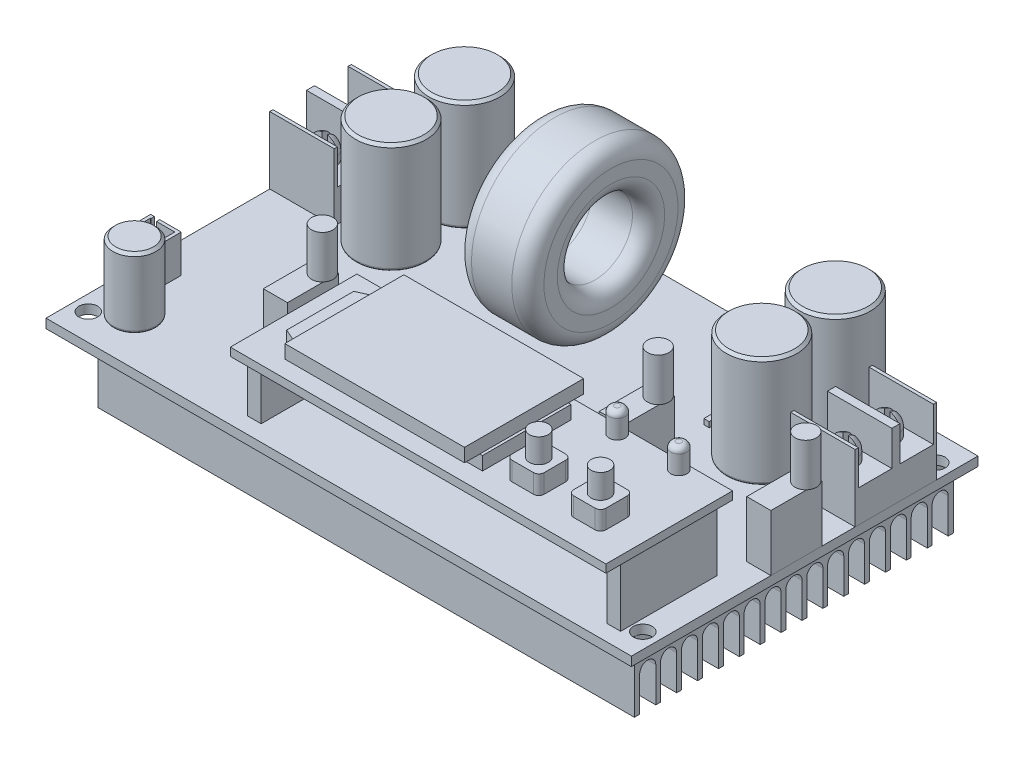
SolidWorks part; units mm, degrees
ref_plane "Alzado" through (0, 0, 0) normal (0, 0, 1) x (1, 0, 0)
ref_plane "Planta" through (0, 0, 0) normal (0, 1, 0) x (1, 0, 0)
ref_plane "Vista lateral" through (0, 0, 0) normal (1, 0, 0) x (0, 0, -1)
sketch "Croquis1" plane through (0, 0, 0) normal (0, 1, 0) x (1, 0, 0)
  line L0 (0, -32.3) -> (0, 32.3) construction
  line L1 (-54.55, 32.3) -> (54.55, 32.3)
  line L2 (-54.55, 32.3) -> (-54.55, -32.3)
  line L3 (-54.55, -32.3) -> (54.55, -32.3)
  line L4 (54.55, 32.3) -> (54.55, -32.3)
  line L5 (-54.55, 32.3) -> (54.55, -32.3) construction
  line L6 (-54.55, -32.3) -> (54.55, 32.3) construction
  line L7 (-54.55, 0) -> (54.55, 0) construction
  circle A0 centre (51.675, 27.3) radius 1.75
  circle A1 centre (51.675, -27.3) radius 1.75
  circle A2 centre (-51.675, -27.3) radius 1.75
  circle A3 centre (-51.675, 27.3) radius 1.75
  point P0 (0, 0)
  point P9 (0, 0)
  point P12 (0, 0)
  dimension "D3" = 3.5
  dimension "D1" = 109.1
  dimension "D2" = 64.6
  dimension "D4" = 5
  dimension "D5" = 103.35
extrude "Saliente-Extruir1" add sketch "Croquis1" along normal blind 1.7
sketch "Croquis2" plane through (0, 1.7, 0) normal (0, 1, 0) x (1, 0, 0)
  line L0 (54.55, 32.3) -> (-54.55, 32.3) construction
  line L2 (-54.55, 32.3) -> (-54.55, -32.3) construction
  circle A0 centre (-34.55, 25.7) radius 6.6
  circle A1 centre (-34.55, 12) radius 6.6
  point P8 (-34.55, 32.3)
  point P10 (-34.55, 19.1)
  point P18 (-34.55, 19.1)
  point P25 (-34.55, 18.6)
  dimension "D1" = 13.2
  dimension "D3" = 20
  dimension "D4" = 0.5
extrude "Saliente-Extruir4" add sketch "Croquis2" along normal blind 20.5 separate body
sketch "Croquis3" plane through (0, 1.7, 0) normal (0, 1, 0) x (1, 0, 0)
  line L0 (-54.55, 32.3) -> (-54.55, -32.3) construction
  line L1 (-54.55, 24.6) -> (-42.55, 24.6)
  line L2 (-54.55, 24.6) -> (-54.55, 9.4)
  line L3 (-54.55, 9.4) -> (-42.55, 9.4)
  line L4 (-42.55, 24.6) -> (-42.55, 9.4)
  line L5 (54.55, 32.3) -> (-54.55, 32.3) construction
  dimension "D1" = 15.2
  dimension "D2" = 12
  dimension "D3" = 7.7
extrude "Saliente-Extruir5" add sketch "Croquis3" along normal blind 6 separate body
sketch "Croquis4" plane through (0, 7.7, 0) normal (0, 1, 0) x (1, 0, 0)
  line L1 (-54.55, 24.6) -> (-42.55, 24.6)
  line L2 (-54.55, 24.6) -> (-54.55, 24)
  line L3 (-54.55, 24) -> (-42.55, 24)
  line L4 (-42.55, 24.6) -> (-42.55, 24)
  line L5 (-54.55, 24.6) -> (-54.55, 9.4) construction
  line L10 (-54.55, 17.75) -> (-42.55, 17.75)
  line L11 (-54.55, 17.75) -> (-54.55, 16.25)
  line L12 (-54.55, 16.25) -> (-42.55, 16.25)
  line L13 (-42.55, 17.75) -> (-42.55, 16.25)
  line L14 (-54.55, 17) -> (-42.55, 17) construction
  line L15 (-54.55, 10) -> (-42.55, 10)
  line L16 (-42.55, 9.4) -> (-42.55, 10)
  line L17 (-54.55, 9.4) -> (-42.55, 9.4)
  line L18 (-54.55, 9.4) -> (-54.55, 10)
  line L19 (-42.55, 9.4) -> (-42.55, 24.6) construction
  point P20 (-54.55, 17)
  point P22 (-54.55, 17)
  dimension "D1" = 1.5
  dimension "D2" = 0.6
extrude "Saliente-Extruir6" add sketch "Croquis4" along normal blind 6.5 separate body
combine bodies "Combinar1" operation type add bodies to combine 103 105 106 104
sketch "Croquis5" plane through (0, 7.7, 0) normal (0, 1, 0) x (1, 0, 0)
  line L0 (-42.55, 17.75) -> (-42.55, 24) construction
  line L1 (-42.55, 24.6) -> (-54.55, 24.6) construction
  line L2 (-54.55, 17) -> (-42.55, 17) construction
  line L3 (-54.55, 17.75) -> (-54.55, 16.25) construction
  line L4 (-42.55, 16.25) -> (-42.55, 17.75) construction
  circle A0 centre (-48.55, 20.875) radius 2.5
  circle A1 centre (-48.55, 13.125) radius 2.5
  point P2 (-48.55, 24.6)
  point P3 (-42.55, 20.875)
  dimension "D1" = 5
extrude "Saliente-Extruir7" add sketch "Croquis5" along normal blind 4
fillet "Redondeo1" radius 2.5 2 edges at (-48.55, 11.7, -15.625) (-48.55, 11.7, -18.375)
ref_plane "Plano1" through (0, 12.2, 0) normal (0, 1, 0) x (1, 0, 0)
sketch "Croquis6" plane through (0, 12.2, 0) normal (0, 1, 0) x (1, 0, 0)
  line L0 (-48.05, 21.375) -> (-46.1005, 21.375)
  line L1 (-49.05, 23.3245) -> (-48.05, 23.3245)
  line L2 (-49.05, 23.3245) -> (-49.05, 21.375)
  line L3 (-49.05, 18.4255) -> (-48.05, 18.4255)
  line L4 (-48.05, 23.3245) -> (-48.05, 21.375)
  line L5 (-50.9995, 21.375) -> (-49.05, 21.375)
  line L6 (-50.9995, 21.375) -> (-50.9995, 20.375)
  line L7 (-50.9995, 20.375) -> (-49.05, 20.375)
  line L8 (-46.1005, 21.375) -> (-46.1005, 20.375)
  line L9 (-49.05, 20.375) -> (-49.05, 18.4255)
  line L10 (-48.05, 20.375) -> (-46.1005, 20.375)
  line L11 (-48.05, 20.375) -> (-48.05, 18.4255)
  line L12 (-54.55, 17) -> (-42.55, 17) construction
  line L13 (-54.55, 17.75) -> (-54.55, 16.25) construction
  line L15 (-48.05, 13.625) -> (-48.05, 15.5745)
  line L16 (-48.05, 13.625) -> (-46.1005, 13.625)
  line L17 (-49.05, 13.625) -> (-49.05, 15.5745)
  line L18 (-46.1005, 12.625) -> (-46.1005, 13.625)
  line L19 (-50.9995, 13.625) -> (-49.05, 13.625)
  line L20 (-50.9995, 12.625) -> (-50.9995, 13.625)
  line L21 (-50.9995, 12.625) -> (-49.05, 12.625)
  line L22 (-48.05, 10.6755) -> (-48.05, 12.625)
  line L23 (-49.05, 15.5745) -> (-48.05, 15.5745)
  line L24 (-49.05, 10.6755) -> (-49.05, 12.625)
  line L25 (-49.05, 10.6755) -> (-48.05, 10.6755)
  line L26 (-48.05, 12.625) -> (-46.1005, 12.625)
  line L27 (-42.55, 16.25) -> (-42.55, 17.75) construction
  circle A0 centre (-48.55, 20.875) radius 2.5 construction
  dimension "D1" = 1
extrude "Cortar-Extruir1" cut sketch "Croquis6" against normal blind 2.5
chamfer "Chaflán2" distance 0.5 angle 45 1 edges at (-34.55, 22.2, -19.1)
chamfer "Chaflán3" distance 0.5 angle 45 1 edges at (-34.55, 22.2, -5.4)
fillet "Redondeo2" radius 0.5 1 edges at (-34.55, 1.7, -5.4)
fillet "Redondeo3" radius 0.5 1 edges at (-34.55, 1.7, -19.1)
sketch "Croquis7" plane through (0, 1.7, 0) normal (0, 1, 0) x (1, 0, 0)
  line L0 (-54.55, 32.3) -> (-54.55, -32.3) construction
  line L1 (-54.55, -12.8) -> (-48.85, -12.8)
  line L2 (-54.55, -12.8) -> (-54.55, -20.3)
  line L3 (-54.55, -20.3) -> (-48.85, -20.3)
  line L4 (-48.85, -12.8) -> (-48.85, -20.3)
  line L5 (-54.55, -32.3) -> (54.55, -32.3) construction
  point P8 (0, -32.3)
  dimension "D1" = 12
  dimension "D2" = 7.5
  dimension "D3" = 5.7
extrude "Saliente-Extruir8" add sketch "Croquis7" along normal blind 7 separate body
shell "Vaciado1" thickness 0.6 removed face at (-51.7, 8.7, 16.55)
sketch "Croquis8" plane through (0, 0, 20.3) normal (0, 0, 1) x (1, 0, 0)
  line L0 (-54.55, 8.7) -> (-48.85, 8.7) construction
  line L1 (-53.85, 8.7) -> (-52.85, 8.7)
  line L2 (-53.85, 8.7) -> (-53.85, 5.2)
  line L3 (-53.85, 5.2) -> (-52.85, 5.2)
  line L4 (-52.85, 8.7) -> (-52.85, 5.2)
  line L5 (-54.55, 8.7) -> (-54.55, 1.7) construction
  dimension "D1" = 3.5
  dimension "D2" = 1
  dimension "D3" = 0.7
extrude "Cortar-Extruir2" cut sketch "Croquis8" against normal up to surface (7.5 mm away) up to face at (-51.7, 5.2, 12.8)
sketch "Croquis9" plane through (-54.55, 0, 0) normal (-1, 0, 0) x (0, 0, 1)
  line L0 (12.8, 8.7) -> (20.3, 8.7) construction
  line L1 (14.8, 8.7) -> (18.3, 8.7)
  line L2 (14.8, 8.7) -> (14.8, 4.7)
  line L3 (14.8, 4.7) -> (18.3, 4.7)
  line L4 (18.3, 8.7) -> (18.3, 4.7)
  line L5 (20.3, 8.7) -> (20.3, 1.7) construction
  line L6 (12.8, 8.7) -> (12.8, 1.7) construction
  line L7 (-32.3, 1.7) -> (32.3, 1.7) construction
  dimension "D1" = 2
  dimension "D2" = 2
  dimension "D3" = 3
extrude "Cortar-Extruir3" cut sketch "Croquis9" against normal up to surface (5.1 mm away) up to face at (-49.45, 5.5, 16.55)
mirror "Simetría2" about plane through (0, 0, 0) normal (1, 0, 0) of bodies 110 102 109
sketch "Croquis11" plane through (0, 1.7, 0) normal (0, 1, 0) x (1, 0, 0)
  line L0 (-54.55, -32.3) -> (54.55, -32.3) construction
  line L1 (-54.55, 32.3) -> (-54.55, -32.3) construction
  circle A0 centre (-46.55, -23.8) radius 4
  dimension "D1" = 8
  dimension "D2" = 8.5
  dimension "D3" = 8
extrude "Saliente-Extruir9" add sketch "Croquis11" along normal blind 13 separate body
fillet "Redondeo4" radius 0.5 1 edges at (-46.55, 1.7, 27.8)
chamfer "Chaflán4" distance 0.5 angle 45 1 edges at (-46.55, 14.7, 27.8)
sketch "Croquis12" plane through (0, 1.7, 0) normal (0, 1, 0) x (1, 0, 0)
  line L0 (54.55, -32.3) -> (54.55, 32.3) construction
  line L1 (-28.55, -8.3) -> (-24.05, -8.3)
  line L2 (-28.55, -8.3) -> (-28.55, -17.8)
  line L3 (-28.55, -17.8) -> (-24.05, -17.8)
  line L4 (-24.05, -8.3) -> (-24.05, -17.8)
  line L5 (22.55, 3.2) -> (27.05, 3.2)
  line L6 (22.55, 3.2) -> (22.55, -6.3)
  line L7 (22.55, -6.3) -> (27.05, -6.3)
  line L8 (27.05, 3.2) -> (27.05, -6.3)
  line L9 (50.05, 3.2) -> (54.55, 3.2)
  line L10 (50.05, 3.2) -> (50.05, -6.3)
  line L11 (50.05, -6.3) -> (54.55, -6.3)
  line L12 (54.55, 3.2) -> (54.55, -6.3)
  line L13 (-54.55, -32.3) -> (54.55, -32.3) construction
  line L14 (-54.55, 32.3) -> (-54.55, -32.3) construction
  dimension "D1" = 9.5
  dimension "D2" = 4.5
  dimension "D3" = 26
  dimension "D4" = 23
  dimension "D5" = 14.5
  dimension "D6" = 26
extrude "Saliente-Extruir10" add sketch "Croquis12" along normal blind 10.5 separate body
sketch "Croquis13" plane through (0, 12.2, 0) normal (0, 1, 0) x (1, 0, 0)
  line L0 (-28.55, -17.8) -> (-24.05, -17.8) construction
  line L1 (-24.05, -17.8) -> (-24.05, -8.3) construction
  line L2 (22.55, -6.3) -> (27.05, -6.3) construction
  line L3 (27.05, -6.3) -> (27.05, 3.2) construction
  line L4 (50.05, -6.3) -> (54.55, -6.3) construction
  line L5 (54.55, -6.3) -> (54.55, 3.2) construction
  circle A0 centre (-25.55, -9.8) radius 2
  circle A1 centre (25.55, 1.7) radius 2
  circle A2 centre (53.05, 1.7) radius 2
  dimension "D1" = 4
  dimension "D2" = 8
  dimension "D3" = 1.5
  dimension "D4" = 8
  dimension "D5" = 1.5
  dimension "D6" = 8
  dimension "D7" = 1.5
extrude "Saliente-Extruir11" add sketch "Croquis13" along normal blind 8
sketch "Croquis14" plane through (0, 1.7, 0) normal (0, 1, 0) x (1, 0, 0)
  line L0 (-54.55, -32.3) -> (54.55, -32.3) construction
  line L1 (-19.95, -11.3) -> (-17.45, -11.3)
  line L2 (-19.95, -11.3) -> (-19.95, -29.3)
  line L3 (-19.95, -29.3) -> (-17.45, -29.3)
  line L4 (-17.45, -11.3) -> (-17.45, -29.3)
  line L5 (47.05, -11.3) -> (49.55, -11.3)
  line L6 (47.05, -11.3) -> (47.05, -29.3)
  line L7 (47.05, -29.3) -> (49.55, -29.3)
  line L8 (49.55, -11.3) -> (49.55, -29.3)
  line L9 (54.55, -32.3) -> (54.55, 32.3) construction
  dimension "D1" = 2.5
  dimension "D2" = 18
  dimension "D3" = 3
  dimension "D4" = 5
  dimension "D5" = 64.5
extrude "Saliente-Extruir12" add sketch "Croquis14" along normal blind 11 separate body
sketch "Croquis15" plane through (0, 12.7, 0) normal (0, 1, 0) x (1, 0, 0)
  line L0 (49.55, -29.3) -> (49.55, -11.3) construction
  line L1 (-20.2, -8.7) -> (49.8, -8.7)
  line L2 (-20.2, -8.7) -> (-20.2, -32.3)
  line L3 (-20.2, -32.3) -> (49.8, -32.3)
  line L4 (49.8, -8.7) -> (49.8, -32.3)
  line L6 (-54.55, -32.3) -> (54.55, -32.3) construction
  dimension "D1" = 70
  dimension "D2" = 0.25
  dimension "D3" = 23.6
extrude "Saliente-Extruir13" add sketch "Croquis15" along normal blind 1.5
sketch "Croquis16" plane through (0, 14.2, 0) normal (0, 1, 0) x (1, 0, 0)
  line L0 (-15.2, -20.55) -> (23.3, -20.55) construction
  line L1 (-15.2, -14.3) -> (-15.2, -26.8)
  line L2 (-15.2, -26.8) -> (-10.7, -28.8)
  line L3 (-10.7, -28.8) -> (23.3, -28.8)
  line L4 (23.3, -28.8) -> (23.3, -12.3)
  line L5 (23.3, -12.3) -> (-10.7, -12.3)
  line L6 (-10.7, -12.3) -> (-15.2, -14.3)
  line L7 (49.8, -32.3) -> (49.8, -8.7) construction
  line L8 (-20.2, -32.3) -> (49.8, -32.3) construction
  point P8 (-15.2, -20.55)
  dimension "D1" = 12.5
  dimension "D2" = 16.5
  dimension "D3" = 34
  dimension "D4" = 4.5
  dimension "D5" = 26.5
  dimension "D6" = 3.5
extrude "Saliente-Extruir14" add sketch "Croquis16" along normal blind 2.5
sketch "Croquis17" plane through (0, 16.7, 0) normal (0, 1, 0) x (1, 0, 0)
  line L1 (-10.7, -9.45) -> (22.8, -9.45)
  line L2 (-10.7, -9.45) -> (-10.7, -31.65)
  line L3 (-10.7, -31.65) -> (22.8, -31.65)
  line L4 (22.8, -9.45) -> (22.8, -31.65)
  line L5 (23.3, -28.8) -> (23.3, -12.3) construction
  point P7 (22.8, -20.55)
  point P11 (23.3, -20.55)
  dimension "D1" = 33.5
  dimension "D2" = 22.2
extrude "Saliente-Extruir15" add sketch "Croquis17" along normal blind 2.5
sketch "Croquis18" plane through (0, 14.2, 0) normal (0, 1, 0) x (1, 0, 0)
  line L0 (-20.2, -32.3) -> (49.8, -32.3) construction
  line L1 (26.8, -21.8) -> (32.8, -21.8)
  line L2 (26.8, -21.8) -> (26.8, -27.8)
  line L3 (26.8, -27.8) -> (32.8, -27.8)
  line L4 (32.8, -21.8) -> (32.8, -27.8)
  line L5 (38.3, -21.8) -> (44.3, -21.8)
  line L6 (38.3, -21.8) -> (38.3, -27.8)
  line L7 (38.3, -27.8) -> (44.3, -27.8)
  line L8 (44.3, -21.8) -> (44.3, -27.8)
  line L9 (49.8, -32.3) -> (49.8, -8.7) construction
  dimension "D1" = 6
  dimension "D2" = 4.5
  dimension "D3" = 5.5
  dimension "D4" = 5.5
extrude "Saliente-Extruir16" add sketch "Croquis18" along normal blind 3.5
sketch "Croquis19" plane through (0, 17.7, 0) normal (0, 1, 0) x (1, 0, 0)
  line L0 (32.8, -21.8) -> (26.8, -21.8) construction
  line L1 (32.8, -27.8) -> (32.8, -21.8) construction
  line L2 (44.3, -21.8) -> (38.3, -21.8) construction
  circle A0 centre (29.8, -24.8) radius 1.75
  circle A1 centre (41.3, -24.8) radius 1.75
  point P4 (32.8, -24.8)
  point P5 (29.8, -21.8)
  point P12 (41.3, -21.8)
  dimension "D1" = 3.5
extrude "Saliente-Extruir17" add sketch "Croquis19" along normal blind 4.5
fillet "Redondeo5" radius 1 8 edges at (26.8, 15.95, 27.8) (32.8, 15.95, 27.8) (26.8, 15.95, 21.8) (32.8, 15.95, 21.8) (38.3, 15.95, 21.8) (44.3, 15.95, 21.8) (38.3, 15.95, 27.8) (44.3, 15.95, 27.8)
ref_plane "Plano2" through (0, 0, -17) normal (0, 0, 1) x (1, 0, 0)
sketch "Croquis20" plane through (0, 0, -17) normal (0, 0, 1) x (1, 0, 0)
  line L0 (54.55, 0) -> (-54.55, 0) construction
  line L1 (1.45, 9.7) -> (-12.05, 9.7)
  line L2 (1.45, 9.7) -> (1.45, 1.2)
  line L3 (1.45, 1.2) -> (-12.05, 1.2)
  line L4 (-12.05, 9.7) -> (-12.05, 1.2)
  line L5 (1.45, 16.7) -> (-12.05, 16.7) construction
  line L6 (-54.55, 1.7) -> (-54.55, 0) construction
  dimension "D1" = 8.5
  dimension "D2" = 13.5
  dimension "D3" = 15.5
  dimension "D4" = 42.5
  dimension "D5" = 9.7
revolve "Revolución1" add sketch "Croquis20" angle 360 about L5
fillet "Redondeo6" radius 3 4 edges at (-12.05, 16.7, -24) (1.45, 16.7, -24) (-12.05, 32.2, -17) (1.45, 32.2, -17)
sketch "Croquis21" plane through (0, 14.2, 0) normal (0, 1, 0) x (1, 0, 0)
  line L0 (31.8, -21.8) -> (27.8, -21.8) construction
  line L1 (43.3, -21.8) -> (39.3, -21.8) construction
  line L2 (49.8, -8.7) -> (-20.2, -8.7) construction
  circle A0 centre (41.3, -10.2) radius 1.5
  circle A1 centre (29.8, -10.2) radius 1.5
  point P4 (41.3, -21.8)
  point P5 (29.8, -21.8)
  point P6 (29.8, -8.7)
  point P11 (41.3, -8.7)
  dimension "D1" = 3
extrude "Saliente-Extruir18" add sketch "Croquis21" along normal blind 4.5
fillet "Redondeo7" radius 1 2 edges at (41.3, 18.7, 11.7) (29.8, 18.7, 11.7)
sketch "Croquis22" plane through (0, 0, 0) normal (0, -1, 0) x (1, 0, 0)
  line L0 (54.55, -32.3) -> (-54.55, -32.3) construction
  line L1 (-50, 27.2) -> (50, 27.2)
  line L2 (-50, 27.2) -> (-50, -32.3)
  line L3 (-50, -32.3) -> (50, -32.3)
  line L4 (50, 27.2) -> (50, -32.3)
  point P8 (0, 27.2)
  dimension "D1" = 100
  dimension "D2" = 59.5
extrude "Saliente-Extruir19" add sketch "Croquis22" along normal blind 13 separate body
sketch "Croquis23" plane through (50, 0, 0) normal (1, 0, 0) x (0, 0, -1)
  line L0 (-26.2, -13) -> (-26.2, -6.5)
  line L1 (32.3, -13) -> (-27.2, -13) construction
  line L2 (-23.2, -6.5) -> (-23.2, -13)
  line L3 (-23.2, -13) -> (-26.2, -13)
  line L4 (-27.2, -13) -> (-27.2, 0) construction
  line L5 (-19.3071, -13) -> (-22.3071, -13)
  line L6 (-22.3071, -13) -> (-22.3071, -6.5)
  line L7 (-19.3071, -6.5) -> (-19.3071, -13)
  line L8 (-15.4143, -13) -> (-18.4143, -13)
  line L9 (-18.4143, -13) -> (-18.4143, -6.5)
  line L10 (-15.4143, -6.5) -> (-15.4143, -13)
  line L11 (-11.5214, -13) -> (-14.5214, -13)
  line L12 (-14.5214, -13) -> (-14.5214, -6.5)
  line L13 (-11.5214, -6.5) -> (-11.5214, -13)
  line L14 (-7.6286, -13) -> (-10.6286, -13)
  line L15 (-10.6286, -13) -> (-10.6286, -6.5)
  line L16 (-7.6286, -6.5) -> (-7.6286, -13)
  line L17 (-3.7357, -13) -> (-6.7357, -13)
  line L18 (-6.7357, -13) -> (-6.7357, -6.5)
  line L19 (-3.7357, -6.5) -> (-3.7357, -13)
  line L20 (0.1571, -13) -> (-2.8429, -13)
  line L21 (-2.8429, -13) -> (-2.8429, -6.5)
  line L22 (0.1571, -6.5) -> (0.1571, -13)
  line L23 (4.05, -13) -> (1.05, -13)
  line L24 (1.05, -13) -> (1.05, -6.5)
  line L25 (4.05, -6.5) -> (4.05, -13)
  line L26 (7.9429, -13) -> (4.9429, -13)
  line L27 (4.9429, -13) -> (4.9429, -6.5)
  line L28 (7.9429, -6.5) -> (7.9429, -13)
  line L29 (11.8357, -13) -> (8.8357, -13)
  line L30 (8.8357, -13) -> (8.8357, -6.5)
  line L31 (11.8357, -6.5) -> (11.8357, -13)
  line L32 (15.7286, -13) -> (12.7286, -13)
  line L33 (12.7286, -13) -> (12.7286, -6.5)
  line L34 (15.7286, -6.5) -> (15.7286, -13)
  line L35 (19.6214, -13) -> (16.6214, -13)
  line L36 (16.6214, -13) -> (16.6214, -6.5)
  line L37 (19.6214, -6.5) -> (19.6214, -13)
  line L38 (23.5143, -13) -> (20.5143, -13)
  line L39 (20.5143, -13) -> (20.5143, -6.5)
  line L40 (23.5143, -6.5) -> (23.5143, -13)
  line L41 (27.4071, -13) -> (24.4071, -13)
  line L42 (24.4071, -13) -> (24.4071, -6.5)
  line L43 (27.4071, -6.5) -> (27.4071, -13)
  line L44 (31.3, -13) -> (28.3, -13)
  line L45 (28.3, -13) -> (28.3, -6.5)
  line L46 (31.3, -6.5) -> (31.3, -13)
  line L47 (32.3, -13) -> (32.3, 0) construction
  arc A0 (-26.2, -6.5) -> (-23.2, -6.5) centre (-24.7, -6.5) cw
  arc A1 (-22.3071, -6.5) -> (-19.3071, -6.5) centre (-20.8071, -6.5) cw
  arc A2 (-18.4143, -6.5) -> (-15.4143, -6.5) centre (-16.9143, -6.5) cw
  arc A3 (-14.5214, -6.5) -> (-11.5214, -6.5) centre (-13.0214, -6.5) cw
  arc A4 (-10.6286, -6.5) -> (-7.6286, -6.5) centre (-9.1286, -6.5) cw
  arc A5 (-6.7357, -6.5) -> (-3.7357, -6.5) centre (-5.2357, -6.5) cw
  arc A6 (-2.8429, -6.5) -> (0.1571, -6.5) centre (-1.3429, -6.5) cw
  arc A7 (1.05, -6.5) -> (4.05, -6.5) centre (2.55, -6.5) cw
  arc A8 (4.9429, -6.5) -> (7.9429, -6.5) centre (6.4429, -6.5) cw
  arc A9 (8.8357, -6.5) -> (11.8357, -6.5) centre (10.3357, -6.5) cw
  arc A10 (12.7286, -6.5) -> (15.7286, -6.5) centre (14.2286, -6.5) cw
  arc A11 (16.6214, -6.5) -> (19.6214, -6.5) centre (18.1214, -6.5) cw
  arc A12 (20.5143, -6.5) -> (23.5143, -6.5) centre (22.0143, -6.5) cw
  arc A13 (24.4071, -6.5) -> (27.4071, -6.5) centre (25.9071, -6.5) cw
  arc A14 (28.3, -6.5) -> (31.3, -6.5) centre (29.8, -6.5) cw
  point P6 (-24.7, -5)
  dimension "D1" = 8
  dimension "D2" = 3
  dimension "D3" = 1
  dimension "D5" = 1
  dimension "D4" = 15
extrude "Cortar-Extruir4" cut sketch "Croquis23" against normal up to surface (100 mm away) up to face at (-50, -6.5, -2.55)
sketch "Croquis24" plane through (0, 1.7, 0) normal (0, 1, 0) x (1, 0, 0)
  line L0 (54.55, 32.3) -> (-54.55, 32.3) construction
  line L1 (23.953, 13.8) -> (24.953, 13.8)
  line L2 (23.953, 13.8) -> (23.953, 11.8)
  line L3 (23.953, 11.8) -> (24.953, 11.8)
  line L4 (24.953, 13.8) -> (24.953, 11.8)
  circle A0 centre (34.55, 12) radius 6.6 construction
  point P6 (27.953, 11.8)
  point P7 (0, 0)
  point P10 (27.95, 12)
  point P11 (28.1162, 10.5281)
  point P12 (27.95, 12)
  point P13 (27.9568, 12.2989)
  point P14 (27.95, 12)
  point P15 (0, 0)
  point P16 (0, 0)
  dimension "D1" = 2
  dimension "D2" = 1
  dimension "D3" = 18.5
  dimension "D4" = 3
extrude "Saliente-Extruir20" add sketch "Croquis24" along normal blind 1
